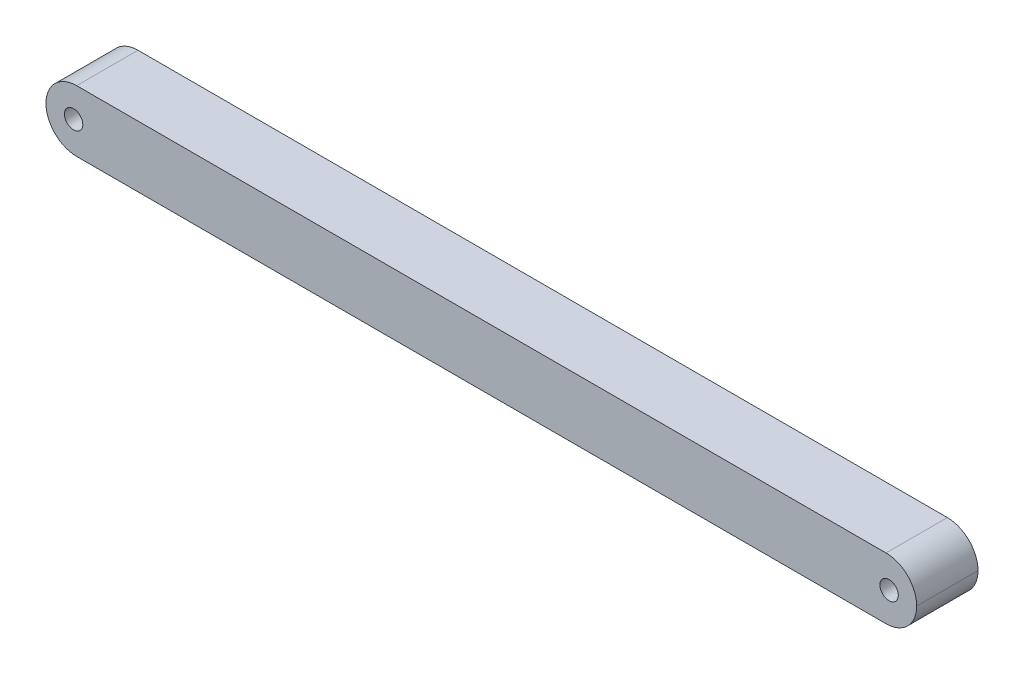
SolidWorks part; units mm, degrees
ref_plane "Front Plane" through (0, 0, 0) normal (0, 0, 1) x (1, 0, 0)
ref_plane "Top Plane" through (0, 0, 0) normal (0, 1, 0) x (1, 0, 0)
ref_plane "Right Plane" through (0, 0, 0) normal (1, 0, 0) x (0, 0, -1)
sketch "Sketch1" plane through (0, 0, 0) normal (0, 0, 1) x (1, 0, 0)
  line L0 (0, 5) -> (142, 5) construction
  line L1 (0, 0) -> (142, 0)
  line L2 (0, 0) -> (0, 10)
  line L3 (0, 10) -> (142, 10)
  line L4 (142, 0) -> (142, 10)
  line L5 (0, 5) -> (3, 5)
  line L6 (139, 5) -> (142, 5)
  circle A0 centre (137.5, 5) radius 1.5
  circle A1 centre (4.5, 5) radius 1.5
  dimension "D3" = 3
  dimension "D4" = 3
  dimension "D1" = 10
  dimension "D2" = 142
  dimension "D5" = 3
  dimension "D6" = 3
extrude "Boss-Extrude1" add sketch "Sketch1" along normal blind 10 contours A1 L0 A0 L6 L4 L3 L2 L5 | L0 A1 L5 L2 L1 L4 L6 A0 region at (71, 7.5187, 0) region at (71, 2.4813, 0)
fillet "Fillet2" radius 5 1 edges at (0, 10, 5) type face fillet first side face at (71, 10, 5) second side face at (0, 5, 5)
fillet "Fillet3" radius 5 1 edges at (0, 0, 5) type face fillet first side face at (71, 0, 5) second side face at (0, 2.5, 5)
fillet "Fillet4" radius 5 1 edges at (142, 10, 5) type face fillet first side face at (73.5, 10, 5) second side face at (142, 5, 5)
fillet "Fillet5" radius 5 1 edges at (142, 0, 5) type face fillet first side face at (73.5, 0, 5) second side face at (142, 2.5, 5)
